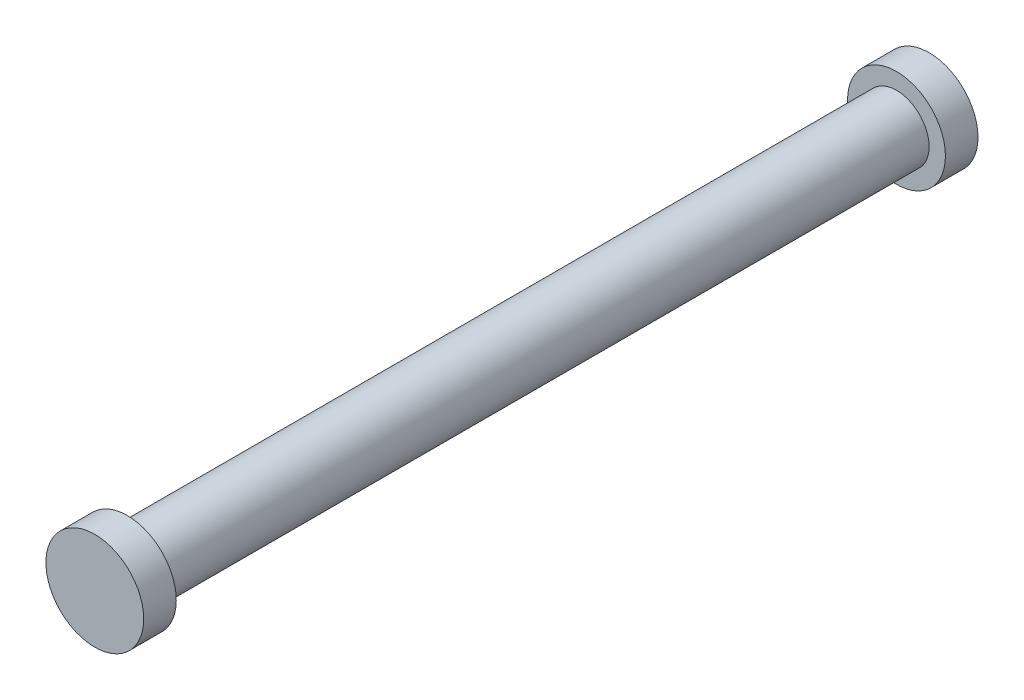
SolidWorks part; units mm, degrees
ref_plane "Front Plane" through (0, 0, 0) normal (0, 0, 1) x (1, 0, 0)
ref_plane "Top Plane" through (0, 0, 0) normal (0, 1, 0) x (1, 0, 0)
ref_plane "Right Plane" through (0, 0, 0) normal (1, 0, 0) x (0, 0, -1)
sketch "Sketch1" plane through (0, 0, 0) normal (0, 0, 1) x (1, 0, 0)
  circle A0 centre (0, 0) radius 5
  circle A1 centre (0, 0) radius 7.5
  dimension "D1" = 10
  dimension "D2" = 15
extrude "Boss-Extrude1" add sketch "Sketch1" along normal blind 128 contours A0 | A1 A0 region at (0, 0, 0) region at (-7.2879, 0, 0)
extrude "Cut-Extrude1" cut sketch "Sketch1<6>" along normal offset from surface (118 mm away) 5 from offset 5 contours A1 A0 region at (-7.2879, 0, 0) up to face at (7.5, 0, 128)
sketch "Sketch1<6>" plane through (0, 0, 0) normal (0, 0, 1) x (1, 0, 0) same geometry as "Sketch1"
